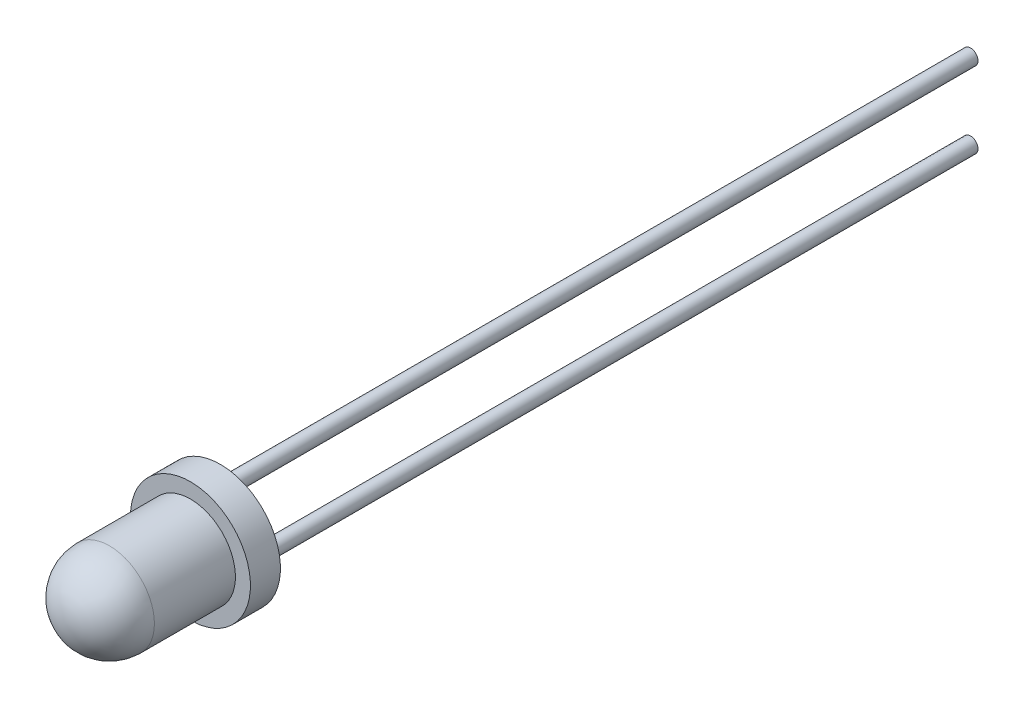
SolidWorks part; units mm, degrees
ref_plane "Спереди" through (0, 0, 0) normal (0, 0, 1) x (1, 0, 0)
ref_plane "Сверху" through (0, 0, 0) normal (0, 1, 0) x (1, 0, 0)
ref_plane "Справа" through (0, 0, 0) normal (1, 0, 0) x (0, 0, -1)
sketch "Эскиз1" plane through (0, 0, 0) normal (0, 0, 1) x (1, 0, 0)
  circle A0 centre (0, 0) radius 1.5
  dimension "D1" = 3
extrude "Бобышка-Вытянуть1" add sketch "Эскиз1" along normal blind 4.2
fillet "Скругление1" radius 1.5 1 edges at (1.5, 0, 4.2)
sketch "Эскиз2" plane through (0, 0, 0) normal (0, 0, -1) x (-1, 0, 0)
  circle A0 centre (0, 0) radius 2
  dimension "D1" = 4
extrude "Бобышка-Вытянуть2" add sketch "Эскиз2" along normal blind 1
sketch "Эскиз3" plane through (0, 0, -1) normal (0, 0, -1) x (-1, 0, 0)
  circle A0 centre (0, 0) radius 1.5
  dimension "D1" = 3
extrude "Бобышка-Вытянуть3" add sketch "Эскиз3" along normal blind 0.5
chamfer "Фаска1" distance 0.5 angle 45 1 edges at (-1.5, 0, -1.5)
sketch "Эскиз4" plane through (0, 0, -1.5) normal (0, 0, -1) x (-1, 0, 0)
  line L0 (0, -1.27) -> (0, 1.27) construction
  circle A0 centre (0, 1.27) radius 0.25
  circle A1 centre (0, -1.27) radius 0.25
  point P6 (0, 0)
  dimension "D1" = 2.54
extrude "Бобышка-Вытянуть4" add sketch "Эскиз4" along normal blind 24.5 and the other way blind 0.5
